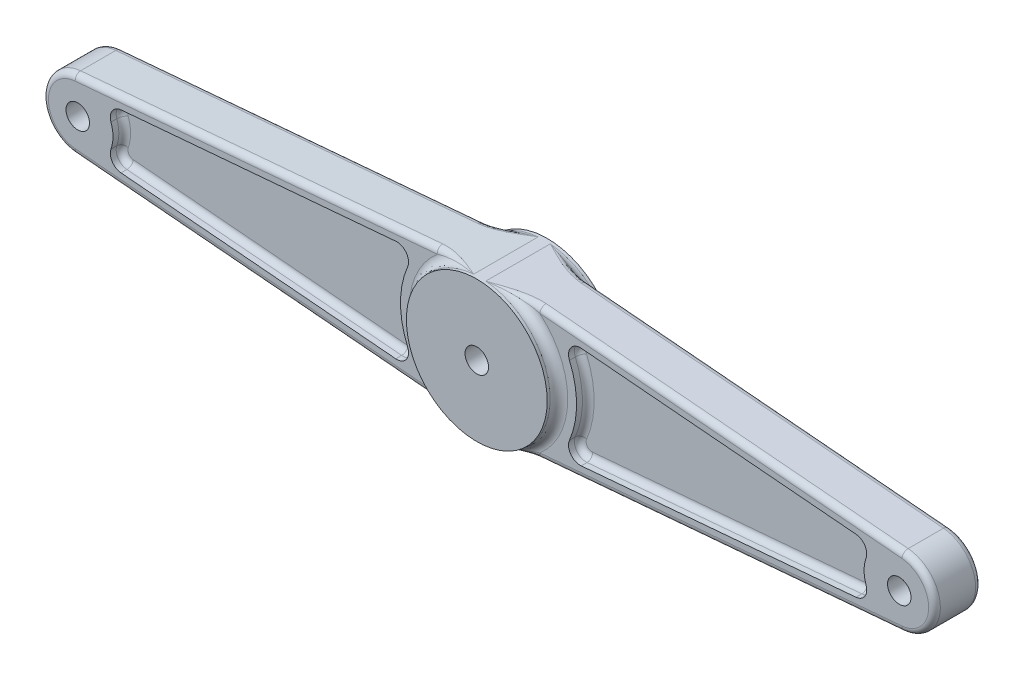
SolidWorks part; units mm, degrees
ref_plane "Front Plane" through (0, 0, 0) normal (0, 0, 1) x (1, 0, 0)
ref_plane "Top Plane" through (0, 0, 0) normal (0, 1, 0) x (1, 0, 0)
ref_plane "Right Plane" through (0, 0, 0) normal (1, 0, 0) x (0, 0, -1)
sketch "Sketch1" plane through (0, 0, 0) normal (0, 0, 1) x (1, 0, 0)
  circle A0 centre (0, 0) radius 12
  dimension "D1" = 24
extrude "Boss-Extrude1" add sketch "Sketch1" along normal mid plane 12
sketch "Sketch2" plane through (0, 0, 0) normal (0, 0, 1) x (1, 0, 0)
  line L0 (0, 0) -> (70, 0) construction
  line L1 (1.0286, 11.9558) -> (70.5143, 5.9779)
  line L2 (1.0286, -11.9558) -> (70.5143, -5.9779)
  circle A0 centre (70, 0) radius 6
  circle A1 centre (70, 0) radius 2
  circle A2 centre (0, 0) radius 12 construction
  arc A3 (1.0286, -11.9558) -> (1.0286, 11.9558) centre (0, 0) ccw
  dimension "D2" = 4
  dimension "D3" = 12
  dimension "D1" = 70
extrude "Boss-Extrude2" add sketch "Sketch2" along normal mid plane 8
mirror "Mirror1" about plane through (0, 0, 0) normal (1, 0, 0) of "Boss-Extrude2"
sketch "Sketch3" plane through (0, 0, 4) normal (0, 0, 1) x (1, 0, 0)
  line L0 (15.8019, 8.6775) -> (62.6254, 4.6492)
  line L1 (0, 0) -> (70, 0) construction
  line L2 (15.8019, -8.6775) -> (62.6254, -4.6492)
  line L3 (1.0286, 11.9558) -> (70.5143, 5.9779) construction
  arc A0 (13.7916, -5.8984) -> (13.7916, 5.8984) centre (0, 0) ccw
  arc A1 (64.3405, 1.9924) -> (64.3405, -1.9924) centre (70, 0) ccw
  circle A2 centre (0, 0) radius 12 construction
  arc A3 (62.6254, 4.6492) -> (64.3405, 1.9924) centre (62.454, 2.6566) cw
  arc A4 (62.6254, -4.6492) -> (64.3405, -1.9924) centre (62.454, -2.6566) ccw
  arc A5 (15.8019, -8.6775) -> (13.7916, -5.8984) centre (15.6305, -6.6848) cw
  arc A6 (15.8019, 8.6775) -> (13.7916, 5.8984) centre (15.6305, 6.6848) ccw
  point P14 (65.8872, 4.3686)
  point P17 (65.8872, -4.3686)
  point P20 (11.9963, -9.0049)
  point P23 (11.9963, 9.0049)
  dimension "D1" = 12
  dimension "D2" = 3
  dimension "D4" = 2
  dimension "D3" = 2
extrude "Cut-Extrude1" cut sketch "Sketch3" against normal blind 2
mirror "Mirror2" about plane through (0, 0, 0) normal (0, 0, 1) of "Cut-Extrude1"
mirror "Mirror3" about plane through (0, 0, 0) normal (1, 0, 0) of "Mirror2", "Cut-Extrude1"
fillet "Fillet1" radius 1 32 edges at (-14.01, -7.857, -2) (-15, 0, -2) (-14.01, 7.857, -2) (-39.2137, 6.6634, -2) (-64.1343, 3.7413, -2) (-64, 0, -2) (-64.1343, -3.7413, -2) (14.01, -7.857, -2) (15, 0, -2) (14.01, 7.857, -2) (39.2137, 6.6634, -2) (64.1343, 3.7413, -2) (64, 0, -2) (64.1343, -3.7413, -2) (14.01, -7.857, 2) (15, 0, 2) (14.01, 7.857, 2) (39.2137, 6.6634, 2) (64.1343, 3.7413, 2) (64, 0, 2) (64.1343, -3.7413, 2) (-14.01, -7.857, 2) (-15, 0, 2) (-14.01, 7.857, 2) (-39.2137, 6.6634, 2) (-64.1343, 3.7413, 2) (-64, 0, 2) (-64.1343, -3.7413, 2) (-39.2137, -6.6634, -2) (39.2137, -6.6634, -2) (39.2137, -6.6634, 2) (-39.2137, -6.6634, 2)
fillet "Fillet2" radius 1.5 4 edges at (-12, 0, 4) (-12, 0, -4) (12, 0, 4) (12, 0, -4)
fillet "Fillet3" radius 1 20 edges at (-4.2015, 11.6829, -4.4638) (-4.2015, -11.6829, -4.4638) (-38.8524, -8.7018, -4) (-76, 0, -4) (4.2015, 11.6829, -4.4638) (4.2015, -11.6829, -4.4638) (38.8524, -8.7018, -4) (76, 0, -4) (76, 0, 4) (4.2015, 11.6829, 4.4638) (4.2015, -11.6829, 4.4638) (38.8524, -8.7018, 4) (-4.2015, 11.6829, 4.4638) (-4.2015, -11.6829, 4.4638) (-38.8524, -8.7018, 4) (-76, 0, 4) (-38.8524, 8.7018, -4) (38.8524, 8.7018, -4) (38.8524, 8.7018, 4) (-38.8524, 8.7018, 4)
sketch "Sketch4" plane through (0, 0, 6) normal (0, 0, 1) x (1, 0, 0)
  circle A0 centre (0, 0) radius 2
  dimension "D1" = 4
extrude "Cut-Extrude2" cut sketch "Sketch4" against normal through all
